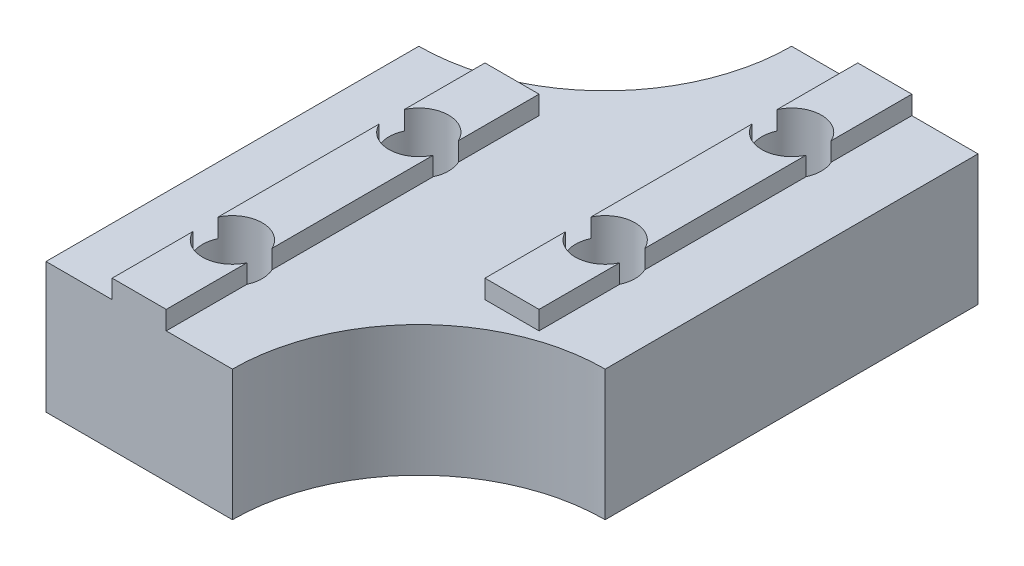
SolidWorks part; units mm, degrees
ref_plane "Front Plane" through (0, 0, 0) normal (0, 0, 1) x (1, 0, 0)
ref_plane "Top Plane" through (0, 0, 0) normal (0, 1, 0) x (1, 0, 0)
ref_plane "Right Plane" through (0, 0, 0) normal (1, 0, 0) x (0, 0, -1)
sketch "Esquisse1" plane through (0, 0, 0) normal (0, 0, 1) x (1, 0, 0)
  line L0 (-5, 0) -> (-5, 7)
  line L1 (-5, 7) -> (-1.45, 7)
  line L2 (-1.45, 7) -> (-1.45, 8)
  line L3 (-1.45, 8) -> (1.45, 8)
  line L4 (1.45, 8) -> (1.45, 7)
  line L5 (1.45, 7) -> (5, 7)
  line L6 (5, 7) -> (5, 0)
  line L7 (5, 0) -> (-5, 0)
  point P11 (0, 0)
  dimension "D1" = 10
  dimension "D2" = 7
  dimension "D3" = 1
  dimension "D4" = 2.9
  dimension "D5" = 3.55
extrude "Main" add sketch "Esquisse1" along normal blind 10
sketch "Esquisse2" plane through (0, 8, 0) normal (0, 1, 0) x (1, 0, 0)
  line L0 (0, -2.2) -> (0, 2.2) construction
  line L2 (-1.45, -10) -> (-5, -10) construction
  circle A1 centre (0, -5) radius 1.6
  dimension "D2" = 5
  dimension "D1" = 3.2
extrude "TopHole" cut sketch "Esquisse2" against normal through all
pattern_linear "LPattern1" count 2 spacing 10 along (0, 0, -1) of bodies 102
pattern_linear "LPattern2" count 2 spacing 10 along (-1, 0, 0) of "Main", "TopHole"
pattern_linear "LPattern3" count 2 spacing 10 along (0, 0, 1) of "TopHole", "LPattern2"
sketch "Sketch1" plane through (0, 8, 0) normal (0, 1, 0) x (1, 0, 0)
  line L0 (-5, 0) -> (-5, 10) construction
  line L1 (5, -20) -> (-5, -20)
  line L2 (5, -20) -> (5, -10)
  line L3 (5, -10) -> (-5, -10)
  line L4 (-5, -20) -> (-5, -10)
  dimension "D1" = 10
extrude "Cut-Extrude1" cut sketch "Sketch1" against normal through all
fillet "Fillet1" radius 10 2 edges at (-5, 3.5, 0) (-5, 3.5, 10)
sketch "Sketch2" plane through (0, 8, 0) normal (0, 1, 0) x (1, 0, 0)
  line L0 (-5, -20) -> (-8.55, -20) construction
  line L1 (-5, 10) -> (-15, 10)
  line L2 (-5, 10) -> (-5, 0)
  line L3 (-5, 0) -> (-15, 0)
  line L4 (-15, 10) -> (-15, 0)
  line L5 (5, -10) -> (-5, -10)
  line L6 (5, -10) -> (5, -20)
  line L7 (5, -20) -> (-5, -20)
  line L8 (-5, -10) -> (-5, -20)
  arc A0 (-1.45, -12.3582) -> (-5, -20) centre (5, -20) ccw construction
  point P14 (-4.8762, -21.5685)
  point P15 (-5, -20)
extrude "Cut-Extrude2" cut sketch "Sketch2" against normal up to surface (1 mm away) up to face at (-5, 7, 5)
